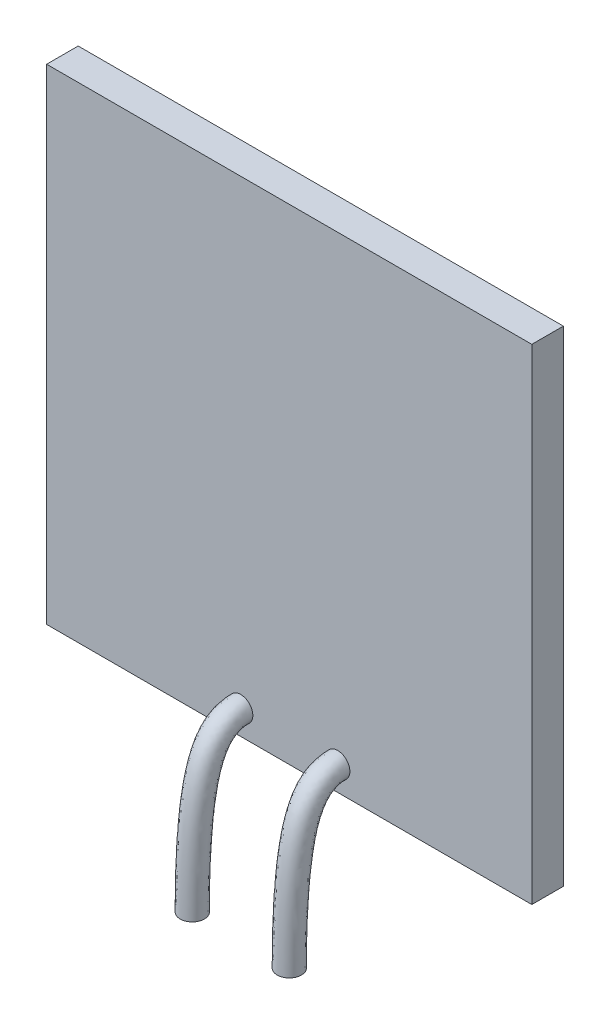
SolidWorks part; units mm, degrees
material "Ceramic Porcelain"
ref_plane "Front Plane" through (0, 0, 0) normal (0, 0, 1) x (1, 0, 0)
ref_plane "Top Plane" through (0, 0, 0) normal (0, 1, 0) x (1, 0, 0)
ref_plane "Right Plane" through (0, 0, 0) normal (1, 0, 0) x (0, 0, -1)
sketch "Sketch1" plane through (0, 0, 0) normal (0, 0, 1) x (1, 0, 0)
  line L1 (-10, -10) -> (10, -10)
  line L2 (-10, -10) -> (-10, 10)
  line L3 (-10, 10) -> (10, 10)
  line L4 (10, -10) -> (10, 10)
  line L5 (-10, -10) -> (10, 10) construction
  line L6 (-10, 10) -> (10, -10) construction
  circle A0 centre (0, 0) radius 3 construction
  point P0 (0, 0)
  dimension "D3" = 6
  dimension "D1" = 20
  dimension "D2" = 20
extrude "Boss-Extrude1" add sketch "Sketch1" along normal mid plane 1.3
sketch "Sketch3" plane through (0, -9.35, 0.65) normal (0, 0, -1) x (1, 0, 0)
  line L0 (-1011.8996, -0.35) -> (48988.1004, -0.35) construction
  line L1 (-10, 0.65) -> (10, 0.65) construction
  line L3 (0, -1000) -> (0, 49000) construction
  circle A0 centre (-2, -0.35) radius 0.5
  circle A1 centre (2, -0.35) radius 0.5
  dimension "D2" = 1
  dimension "D1" = 4
  dimension "D3" = 1
ref_plane "Plane3" through (-2, 0, 0) normal (1, 0, 0) x (0, 0, -1)
sketch "Sketch12" plane through (-2, 0, 0) normal (1, 0, 0) x (0, 0, -1)
  line L1 (-0.65, -9.5) -> (-0.65, -8.5) construction
  line L2 (-0.65, -9) -> (-1.8719, -9) construction
  line L3 (-1.8719, -9) -> (-2.6456, -10.0389) construction
  line L4 (-2.6456, -10.0389) -> (-2.6456, -15.2707) construction
  spline S0 degree 3 poles (-0.65, -9) (-1.8719, -9) (-2.6456, -10.0389) (-2.6456, -15.2707) knots 0 0 0 0 1 1 1 1
  point P1 (-3.2207, -9.9611)
  point P2 (-1.9425, -9.1101)
  point P8 (-2.9678, -10.1713)
  point P9 (-1.9059, -8.9422)
  point P10 (-2.8836, -9.7498)
  point P11 (-1.8719, -8.9483)
  point P12 (-2.6456, -10.0389)
sweep "Sweep2" add profiles "Sketch3" path "Sketch12"
equation "\"CeramicHeater.X\"= 20mm"
equation "\"D1@Sketch1\"=\"CeramicHeater.X\""
equation "\"CeramicHeater.Y\"= 20mm"
equation "\"D2@Sketch1\"=\"CeramicHeater.Y\""
equation "\"CeramicHeater.Z\"= 1.3mm"
equation "\"CeramicHeater.Diam\"= 6mm"
equation "\"D3@Sketch1\"=\"CeramicHeater.Diam\""
equation "\"D1@Boss-Extrude1\"=\"CeramicHeater.Z\""
equation "\"CenterAxesDistance.X\"= 4"
equation "\"D1@Sketch3\"=\"CenterAxesDistance.X\""
